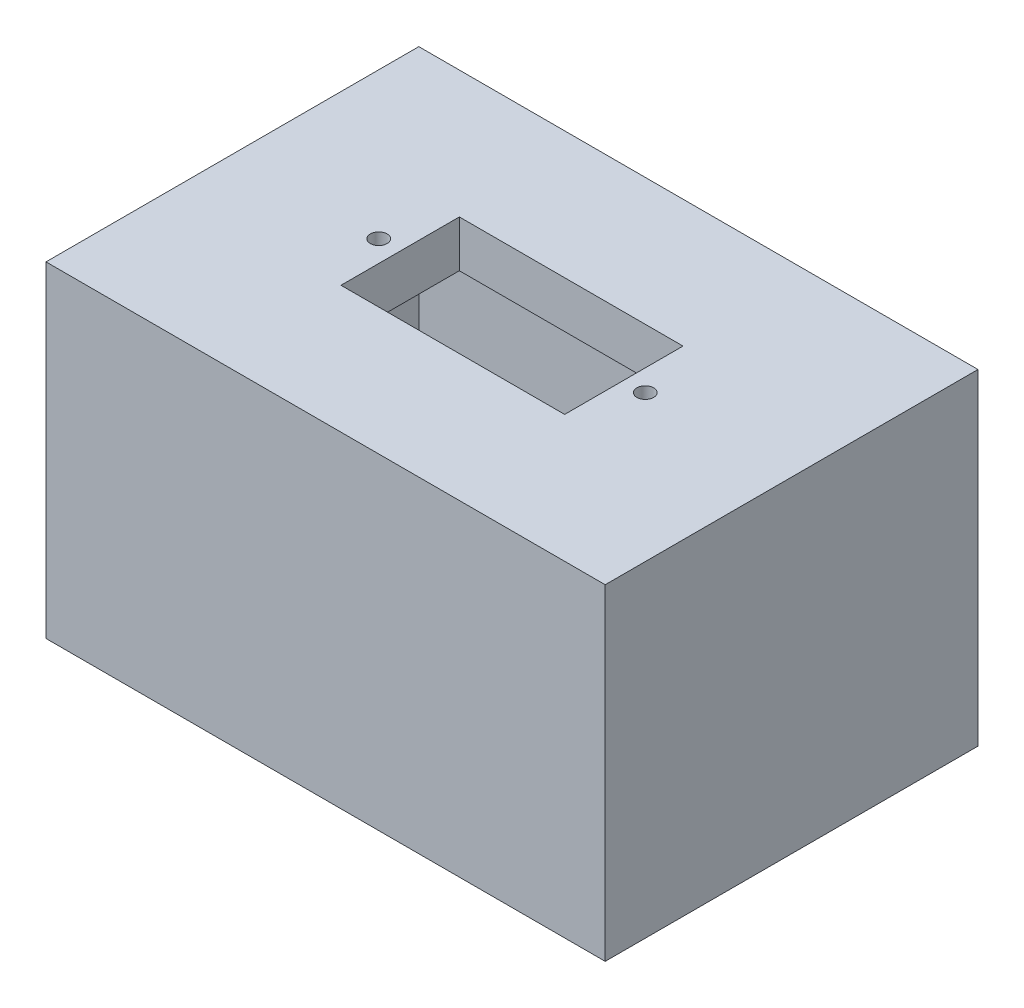
SolidWorks part; units mm, degrees
ref_plane "前视基准面" through (0, 0, 0) normal (0, 0, 1) x (1, 0, 0)
ref_plane "上视基准面" through (0, 0, 0) normal (0, 1, 0) x (1, 0, 0)
ref_plane "右视基准面" through (0, 0, 0) normal (1, 0, 0) x (0, 0, -1)
sketch "草图1" plane through (0, 0, 0) normal (0, 1, 0) x (1, 0, 0)
  line L0 (0, 0) -> (0, 12.535) construction
  line L1 (12, -6.35) -> (-12, -6.35)
  line L2 (12, -6.35) -> (12, 6.35)
  line L3 (12, 6.35) -> (-12, 6.35)
  line L4 (-12, -6.35) -> (-12, 6.35)
  line L5 (12, -6.35) -> (-12, 6.35) construction
  line L6 (12, 6.35) -> (-12, -6.35) construction
  line L7 (18.5533, -9.6358) -> (-18.5533, -9.6358)
  line L8 (18.5533, -9.6358) -> (18.5533, 9.6358)
  line L9 (18.5533, 9.6358) -> (-18.5533, 9.6358)
  line L10 (-18.5533, -9.6358) -> (-18.5533, 9.6358)
  line L11 (18.5533, -9.6358) -> (-18.5533, 9.6358) construction
  line L12 (18.5533, 9.6358) -> (-18.5533, -9.6358) construction
  line L13 (-14.3, 0) -> (0, 0) construction
  circle A0 centre (-14.3, 0) radius 0.9
  circle A2 centre (14.3, 0) radius 0.9
  point P0 (0, 0)
  point P6 (0, 0)
  dimension "D4" = 1.8
  dimension "D1" = 24
  dimension "D2" = 12.7
  dimension "D3" = 14.3
extrude "凸台-拉伸1" add sketch "草图1" along normal blind 5
ref_axis "基准轴1" [suppressed] through (0, 5.25, 0) along (0, -1, 0)
ref_plane "基准面2" [suppressed] through (0, 0, 0) normal (-0.5093, 0, 0.8606) x (0, -1, 0)
sketch "草图2" [suppressed] plane through (0, 0, 0) normal (0.5093, 0, -0.8606) x (-0.8606, 0, -0.5093)
  line L1 (20.8744, 5) -> (20.8744, 0) construction
  line L4 (0, -1.05) -> (0, 8.4021) construction
  line L5 (-13.5611, 5) -> (-13.5611, 0) construction
  line L6 (-13.5611, 5) -> (-13.5611, 0) construction
  line L7 (20.4583, 2.5) -> (-20.4583, 2.5) construction
  line L9 (0, 5.25) -> (0, -0.25) construction
  spline S0 degree 3 poles (-13.5611, 2.5) (-21.5757, 2.496) (-28.5203, -1.089) (-28.1083, -15.0942) (-28.178, -25.5) knots 0 0 0 0 0.354063 1 1 1 1
  point P3 (20.8744, 2.5)
  dimension "D1" = 28.178
  dimension "D2" = 28
sweep "扫描1" [suppressed] add path "草图2" circular profile diameter 6 parameters "D3"=6
sketch "草图35" [suppressed] plane through (0.1482, -25.6877, 0.0877) normal (0.0058, -1, 0.0034) x (1, 0.0058, 0)
  line L0 (-1153.5754, -682.6456) -> (1153.6178, 682.6707) construction
  circle A0 centre (24.1054, 14.2647) radius 1.475
  dimension "D1" = 2.95
extrude "切除-拉伸1" [suppressed] cut sketch "草图35" against normal blind 6
mirror "镜向1" [suppressed] about plane through (0, 0, 0) normal (0, 0, 1)
mirror "镜向2" [suppressed] about plane through (0, 0, 0) normal (1, 0, 0)
sketch "草图36" plane through (0, 5, 0) normal (0, 1, 0) x (1, 0, 0)
  line L0 (-18.5533, -9.6358) -> (18.5533, -9.6358) construction
  line L1 (30, -20) -> (-30, -20)
  line L2 (30, -20) -> (30, 20)
  line L3 (30, 20) -> (-30, 20)
  line L4 (-30, -20) -> (-30, 20)
  line L5 (30, -20) -> (-30, 20) construction
  line L6 (30, 20) -> (-30, -20) construction
  line L7 (18.5533, -9.6358) -> (18.5533, 9.6358) construction
  line L8 (18.5533, 9.6358) -> (-18.5533, 9.6358) construction
  line L9 (-18.5533, 9.6358) -> (-18.5533, -9.6358) construction
  line L10 (-18.5533, -9.6358) -> (18.5533, -9.6358)
  line L11 (18.5533, -9.6358) -> (18.5533, 9.6358)
  line L12 (18.5533, 9.6358) -> (-18.5533, 9.6358)
  line L13 (-18.5533, 9.6358) -> (-18.5533, -9.6358)
  point P0 (0, 0)
  dimension "D1" = 40
  dimension "D2" = 60
extrude "凸台-拉伸2" add sketch "草图36" against normal blind 5
sketch "草图45" plane through (0, 0, 0) normal (0, -1, 0) x (1, 0, 0)
  line L0 (30, -20) -> (-30, -20) construction
  line L1 (30, 20) -> (30, -20) construction
  line L2 (-30, 20) -> (30, 20) construction
  line L3 (-30, -20) -> (-30, 20) construction
  line L4 (30, -20) -> (-30, -20)
  line L5 (30, 20) -> (30, -20)
  line L6 (-30, 20) -> (30, 20)
  line L7 (-30, -20) -> (-30, 20)
  line L9 (27, -17) -> (-27, -17)
  line L10 (27, -17) -> (27, 17)
  line L11 (27, 17) -> (-27, 17)
  line L12 (-27, -17) -> (-27, 17)
  line L13 (27, -17) -> (-27, 17) construction
  line L14 (27, 17) -> (-27, -17) construction
  point P3 (0, 0)
  dimension "D1" = 3
  dimension "D2" = 3
extrude "凸台-拉伸3" add sketch "草图45" along normal blind 30
